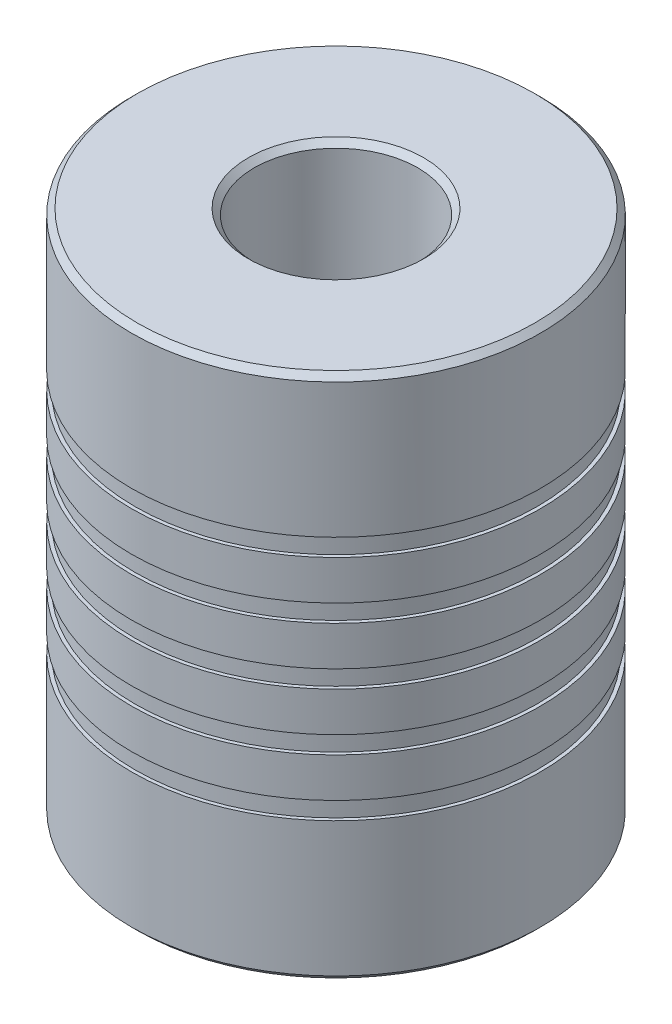
SolidWorks part; units mm, degrees
material "AISI 304"
ref_plane "Спереди" through (0, 0, 0) normal (0, 0, 1) x (1, 0, 0)
ref_plane "Сверху" through (0, 0, 0) normal (0, 1, 0) x (1, 0, 0)
ref_plane "Справа" through (0, 0, 0) normal (1, 0, 0) x (0, 0, -1)
ref_axis "ОсьX" through (-88.99, 0, 0) along (1, 0, 0)
ref_axis "ОсьZ" through (0, 55, 0) along (0, -1, 0)
ref_axis "ОсьY" through (0, 0, -88.99) along (0, 0, 1)
sketch "Эскиз1" plane through (0, 0, 0) normal (0, 0, 1) x (1, 0, 0)
  line L0 (0, 53.651) -> (0, -39.6861) construction
  line L1 (7, 22.5) -> (17.5, 22.5)
  line L2 (17.5, 22.5) -> (17.5, 10.5)
  line L3 (17.5, 10.5) -> (17.2, 10.5)
  line L4 (17.2, 10.5) -> (17.2, 9)
  line L5 (17.2, 9) -> (17.5, 9)
  line L6 (17.5, 9) -> (17.5, 5.625)
  line L7 (17.5, 5.625) -> (17.2, 5.625)
  line L8 (17.2, 5.625) -> (17.2, 4.125)
  line L9 (17.2, 4.125) -> (17.5, 4.125)
  line L10 (17.5, 4.125) -> (17.5, 0.75)
  line L11 (17.5, 0.75) -> (17.2, 0.75)
  line L12 (17.2, 0.75) -> (17.2, -0.75)
  line L13 (0, 0) -> (26.5009, 0) construction
  line L14 (17.5, -0.75) -> (17.2, -0.75)
  line L15 (17.5, -4.125) -> (17.5, -0.75)
  line L16 (17.2, -4.125) -> (17.5, -4.125)
  line L17 (17.2, -5.625) -> (17.2, -4.125)
  line L18 (17.5, -5.625) -> (17.2, -5.625)
  line L19 (17.5, -9) -> (17.5, -5.625)
  line L20 (17.2, -9) -> (17.5, -9)
  line L21 (17.2, -10.5) -> (17.2, -9)
  line L22 (17.5, -10.5) -> (17.2, -10.5)
  line L23 (17.5, -22.5) -> (17.5, -10.5)
  line L24 (7, -22.5) -> (17.5, -22.5)
  line L25 (7, 22.5) -> (7, -22.5)
  point P20 (17.2, 0)
  dimension "D1" = 14
  dimension "D2" = 35
  dimension "D3" = 1.5
  dimension "D4" = 0.3
  dimension "D5" = 45
  dimension "D6" = 12
revolve "Повернуть1" add sketch "Эскиз1" angle 360 mid plane about L0
chamfer "Фаска1" distance 0.5 angle 45 4 edges at (0, -22.5, 7) (0, -22.5, 17.5) (0, 22.5, 7) (0, 22.5, 17.5)
